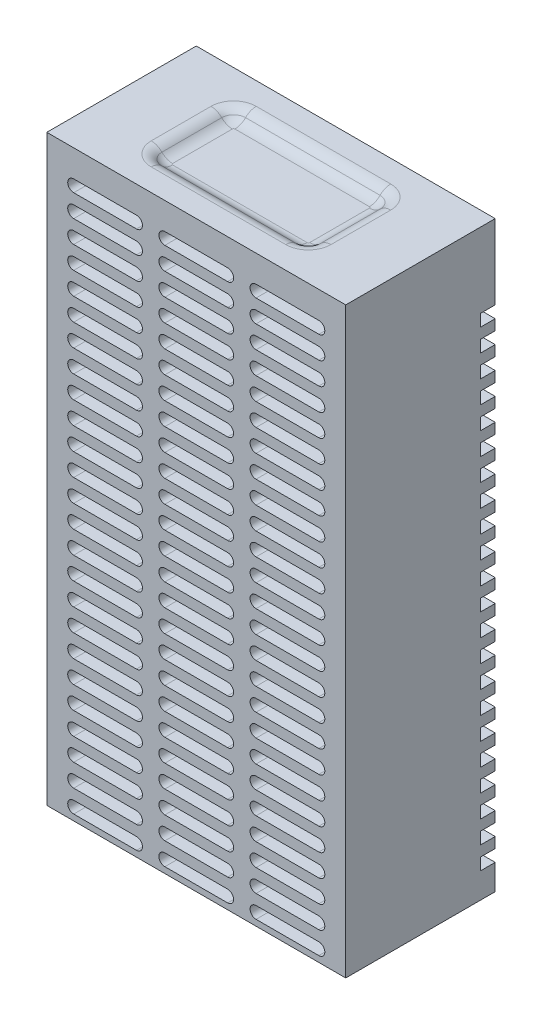
SolidWorks part; units mm, degrees
material "Plain Carbon Steel"
ref_plane "Front Plane" through (0, 0, 0) normal (0, 0, 1) x (1, 0, 0)
ref_plane "Top Plane" through (0, 0, 0) normal (0, 1, 0) x (1, 0, 0)
ref_plane "Right Plane" through (0, 0, 0) normal (1, 0, 0) x (0, 0, -1)
sketch "Sketch1" plane through (0, 0, 0) normal (0, 0, 1) x (1, 0, 0)
  line L1 (50, -97.5) -> (-50, -97.5)
  line L2 (50, -97.5) -> (50, 97.5)
  line L3 (50, 97.5) -> (-50, 97.5)
  line L4 (-50, -97.5) -> (-50, 97.5)
  line L5 (50, -97.5) -> (-50, 97.5) construction
  line L6 (50, 97.5) -> (-50, -97.5) construction
  point P0 (0, 0)
  dimension "D1" = 100
  dimension "D2" = 195
extrude "Boss-Extrude1" add sketch "Sketch1" along normal blind 50
sketch "Sketch2" plane through (0, 0, 50) normal (0, 0, 1) x (1, 0, 0)
  line L0 (-50, 88.5) -> (50, 88.5) construction
  line L1 (-50, 97.5) -> (-50, -97.5) construction
  line L2 (50, -97.5) -> (50, 97.5) construction
  line L3 (50, 97.5) -> (-50, 97.5) construction
  line L4 (0, 97.5) -> (0, -97.5) construction
  line L5 (-50, -97.5) -> (50, -97.5) construction
  line L6 (10.5, 86.5) -> (-10.5, 86.5) construction
  line L7 (10.5, 84.5) -> (-10.5, 84.5)
  line L8 (10.5, 88.5) -> (-10.5, 88.5)
  line L9 (-41, 86.5) -> (-20, 86.5) construction
  line L10 (-41, 88.5) -> (-20, 88.5)
  line L11 (-41, 84.5) -> (-20, 84.5)
  line L12 (41, 86.5) -> (20, 86.5) construction
  line L13 (41, 88.5) -> (20, 88.5)
  line L14 (41, 84.5) -> (20, 84.5)
  line L15 (10.5, 79) -> (-10.5, 79) construction
  line L16 (10.5, 77) -> (-10.5, 77)
  line L17 (10.5, 81) -> (-10.5, 81)
  line L18 (-41, 79) -> (-20, 79) construction
  line L19 (-41, 81) -> (-20, 81)
  line L20 (-41, 77) -> (-20, 77)
  line L21 (41, 79) -> (20, 79) construction
  line L22 (41, 81) -> (20, 81)
  line L23 (41, 77) -> (20, 77)
  line L24 (10.5, 71.5) -> (-10.5, 71.5) construction
  line L25 (10.5, 69.5) -> (-10.5, 69.5)
  line L26 (10.5, 73.5) -> (-10.5, 73.5)
  line L27 (-41, 71.5) -> (-20, 71.5) construction
  line L28 (-41, 73.5) -> (-20, 73.5)
  line L29 (-41, 69.5) -> (-20, 69.5)
  line L30 (41, 71.5) -> (20, 71.5) construction
  line L31 (41, 73.5) -> (20, 73.5)
  line L32 (41, 69.5) -> (20, 69.5)
  line L33 (10.5, 64) -> (-10.5, 64) construction
  line L34 (10.5, 62) -> (-10.5, 62)
  line L35 (10.5, 66) -> (-10.5, 66)
  line L36 (-41, 64) -> (-20, 64) construction
  line L37 (-41, 66) -> (-20, 66)
  line L38 (-41, 62) -> (-20, 62)
  line L39 (41, 64) -> (20, 64) construction
  line L40 (41, 66) -> (20, 66)
  line L41 (41, 62) -> (20, 62)
  line L42 (10.5, 56.5) -> (-10.5, 56.5) construction
  line L43 (10.5, 54.5) -> (-10.5, 54.5)
  line L44 (10.5, 58.5) -> (-10.5, 58.5)
  line L45 (-41, 56.5) -> (-20, 56.5) construction
  line L46 (-41, 58.5) -> (-20, 58.5)
  line L47 (-41, 54.5) -> (-20, 54.5)
  line L48 (41, 56.5) -> (20, 56.5) construction
  line L49 (41, 58.5) -> (20, 58.5)
  line L50 (41, 54.5) -> (20, 54.5)
  line L51 (10.5, 49) -> (-10.5, 49) construction
  line L52 (10.5, 47) -> (-10.5, 47)
  line L53 (10.5, 51) -> (-10.5, 51)
  line L54 (-41, 49) -> (-20, 49) construction
  line L55 (-41, 51) -> (-20, 51)
  line L56 (-41, 47) -> (-20, 47)
  line L57 (41, 49) -> (20, 49) construction
  line L58 (41, 51) -> (20, 51)
  line L59 (41, 47) -> (20, 47)
  line L60 (10.5, 41.5) -> (-10.5, 41.5) construction
  line L61 (10.5, 39.5) -> (-10.5, 39.5)
  line L62 (10.5, 43.5) -> (-10.5, 43.5)
  line L63 (-41, 41.5) -> (-20, 41.5) construction
  line L64 (-41, 43.5) -> (-20, 43.5)
  line L65 (-41, 39.5) -> (-20, 39.5)
  line L66 (41, 41.5) -> (20, 41.5) construction
  line L67 (41, 43.5) -> (20, 43.5)
  line L68 (41, 39.5) -> (20, 39.5)
  line L69 (10.5, 34) -> (-10.5, 34) construction
  line L70 (10.5, 32) -> (-10.5, 32)
  line L71 (10.5, 36) -> (-10.5, 36)
  line L72 (-41, 34) -> (-20, 34) construction
  line L73 (-41, 36) -> (-20, 36)
  line L74 (-41, 32) -> (-20, 32)
  line L75 (41, 34) -> (20, 34) construction
  line L76 (41, 36) -> (20, 36)
  line L77 (41, 32) -> (20, 32)
  line L78 (10.5, 26.5) -> (-10.5, 26.5) construction
  line L79 (10.5, 24.5) -> (-10.5, 24.5)
  line L80 (10.5, 28.5) -> (-10.5, 28.5)
  line L81 (-41, 26.5) -> (-20, 26.5) construction
  line L82 (-41, 28.5) -> (-20, 28.5)
  line L83 (-41, 24.5) -> (-20, 24.5)
  line L84 (41, 26.5) -> (20, 26.5) construction
  line L85 (41, 28.5) -> (20, 28.5)
  line L86 (41, 24.5) -> (20, 24.5)
  line L87 (10.5, 19) -> (-10.5, 19) construction
  line L88 (10.5, 17) -> (-10.5, 17)
  line L89 (10.5, 21) -> (-10.5, 21)
  line L90 (-41, 19) -> (-20, 19) construction
  line L91 (-41, 21) -> (-20, 21)
  line L92 (-41, 17) -> (-20, 17)
  line L93 (41, 19) -> (20, 19) construction
  line L94 (41, 21) -> (20, 21)
  line L95 (41, 17) -> (20, 17)
  line L96 (10.5, 11.5) -> (-10.5, 11.5) construction
  line L97 (10.5, 9.5) -> (-10.5, 9.5)
  line L98 (10.5, 13.5) -> (-10.5, 13.5)
  line L99 (-41, 11.5) -> (-20, 11.5) construction
  line L100 (-41, 13.5) -> (-20, 13.5)
  line L101 (-41, 9.5) -> (-20, 9.5)
  line L102 (41, 11.5) -> (20, 11.5) construction
  line L103 (41, 13.5) -> (20, 13.5)
  line L104 (41, 9.5) -> (20, 9.5)
  line L105 (10.5, 4) -> (-10.5, 4) construction
  line L106 (10.5, 2) -> (-10.5, 2)
  line L107 (10.5, 6) -> (-10.5, 6)
  line L108 (-41, 4) -> (-20, 4) construction
  line L109 (-41, 6) -> (-20, 6)
  line L110 (-41, 2) -> (-20, 2)
  line L111 (41, 4) -> (20, 4) construction
  line L112 (41, 6) -> (20, 6)
  line L113 (41, 2) -> (20, 2)
  line L114 (10.5, -3.5) -> (-10.5, -3.5) construction
  line L115 (10.5, -5.5) -> (-10.5, -5.5)
  line L116 (10.5, -1.5) -> (-10.5, -1.5)
  line L117 (-41, -3.5) -> (-20, -3.5) construction
  line L118 (-41, -1.5) -> (-20, -1.5)
  line L119 (-41, -5.5) -> (-20, -5.5)
  line L120 (41, -3.5) -> (20, -3.5) construction
  line L121 (41, -1.5) -> (20, -1.5)
  line L122 (41, -5.5) -> (20, -5.5)
  line L123 (10.5, -11) -> (-10.5, -11) construction
  line L124 (10.5, -13) -> (-10.5, -13)
  line L125 (10.5, -9) -> (-10.5, -9)
  line L126 (-41, -11) -> (-20, -11) construction
  line L127 (-41, -9) -> (-20, -9)
  line L128 (-41, -13) -> (-20, -13)
  line L129 (41, -11) -> (20, -11) construction
  line L130 (41, -9) -> (20, -9)
  line L131 (41, -13) -> (20, -13)
  line L132 (10.5, -18.5) -> (-10.5, -18.5) construction
  line L133 (10.5, -20.5) -> (-10.5, -20.5)
  line L134 (10.5, -16.5) -> (-10.5, -16.5)
  line L135 (-41, -18.5) -> (-20, -18.5) construction
  line L136 (-41, -16.5) -> (-20, -16.5)
  line L137 (-41, -20.5) -> (-20, -20.5)
  line L138 (41, -18.5) -> (20, -18.5) construction
  line L139 (41, -16.5) -> (20, -16.5)
  line L140 (41, -20.5) -> (20, -20.5)
  line L141 (10.5, -26) -> (-10.5, -26) construction
  line L142 (10.5, -28) -> (-10.5, -28)
  line L143 (10.5, -24) -> (-10.5, -24)
  line L144 (-41, -26) -> (-20, -26) construction
  line L145 (-41, -24) -> (-20, -24)
  line L146 (-41, -28) -> (-20, -28)
  line L147 (41, -26) -> (20, -26) construction
  line L148 (41, -24) -> (20, -24)
  line L149 (41, -28) -> (20, -28)
  line L150 (10.5, -33.5) -> (-10.5, -33.5) construction
  line L151 (10.5, -35.5) -> (-10.5, -35.5)
  line L152 (10.5, -31.5) -> (-10.5, -31.5)
  line L153 (-41, -33.5) -> (-20, -33.5) construction
  line L154 (-41, -31.5) -> (-20, -31.5)
  line L155 (-41, -35.5) -> (-20, -35.5)
  line L156 (41, -33.5) -> (20, -33.5) construction
  line L157 (41, -31.5) -> (20, -31.5)
  line L158 (41, -35.5) -> (20, -35.5)
  line L159 (10.5, -41) -> (-10.5, -41) construction
  line L160 (10.5, -43) -> (-10.5, -43)
  line L161 (10.5, -39) -> (-10.5, -39)
  line L162 (-41, -41) -> (-20, -41) construction
  line L163 (-41, -39) -> (-20, -39)
  line L164 (-41, -43) -> (-20, -43)
  line L165 (41, -41) -> (20, -41) construction
  line L166 (41, -39) -> (20, -39)
  line L167 (41, -43) -> (20, -43)
  line L168 (10.5, -48.5) -> (-10.5, -48.5) construction
  line L169 (10.5, -50.5) -> (-10.5, -50.5)
  line L170 (10.5, -46.5) -> (-10.5, -46.5)
  line L171 (-41, -48.5) -> (-20, -48.5) construction
  line L172 (-41, -46.5) -> (-20, -46.5)
  line L173 (-41, -50.5) -> (-20, -50.5)
  line L174 (41, -48.5) -> (20, -48.5) construction
  line L175 (41, -46.5) -> (20, -46.5)
  line L176 (41, -50.5) -> (20, -50.5)
  line L177 (10.5, -56) -> (-10.5, -56) construction
  line L178 (10.5, -58) -> (-10.5, -58)
  line L179 (10.5, -54) -> (-10.5, -54)
  line L180 (-41, -56) -> (-20, -56) construction
  line L181 (-41, -54) -> (-20, -54)
  line L182 (-41, -58) -> (-20, -58)
  line L183 (41, -56) -> (20, -56) construction
  line L184 (41, -54) -> (20, -54)
  line L185 (41, -58) -> (20, -58)
  line L186 (10.5, -63.5) -> (-10.5, -63.5) construction
  line L187 (10.5, -65.5) -> (-10.5, -65.5)
  line L188 (10.5, -61.5) -> (-10.5, -61.5)
  line L189 (-41, -63.5) -> (-20, -63.5) construction
  line L190 (-41, -61.5) -> (-20, -61.5)
  line L191 (-41, -65.5) -> (-20, -65.5)
  line L192 (41, -63.5) -> (20, -63.5) construction
  line L193 (41, -61.5) -> (20, -61.5)
  line L194 (41, -65.5) -> (20, -65.5)
  line L195 (10.5, -71) -> (-10.5, -71) construction
  line L196 (10.5, -73) -> (-10.5, -73)
  line L197 (10.5, -69) -> (-10.5, -69)
  line L198 (-41, -71) -> (-20, -71) construction
  line L199 (-41, -69) -> (-20, -69)
  line L200 (-41, -73) -> (-20, -73)
  line L201 (41, -71) -> (20, -71) construction
  line L202 (41, -69) -> (20, -69)
  line L203 (41, -73) -> (20, -73)
  line L204 (10.5, -78.5) -> (-10.5, -78.5) construction
  line L205 (10.5, -80.5) -> (-10.5, -80.5)
  line L206 (10.5, -76.5) -> (-10.5, -76.5)
  line L207 (-41, -78.5) -> (-20, -78.5) construction
  line L208 (-41, -76.5) -> (-20, -76.5)
  line L209 (-41, -80.5) -> (-20, -80.5)
  line L210 (41, -78.5) -> (20, -78.5) construction
  line L211 (41, -76.5) -> (20, -76.5)
  line L212 (41, -80.5) -> (20, -80.5)
  line L213 (10.5, -86) -> (-10.5, -86) construction
  line L214 (10.5, -88) -> (-10.5, -88)
  line L215 (10.5, -84) -> (-10.5, -84)
  line L216 (-41, -86) -> (-20, -86) construction
  line L217 (-41, -84) -> (-20, -84)
  line L218 (-41, -88) -> (-20, -88)
  line L219 (41, -86) -> (20, -86) construction
  line L220 (41, -84) -> (20, -84)
  line L221 (41, -88) -> (20, -88)
  line L222 (10.5, -93.5) -> (-10.5, -93.5) construction
  line L223 (10.5, -95.5) -> (-10.5, -95.5)
  line L224 (10.5, -91.5) -> (-10.5, -91.5)
  line L225 (-41, -93.5) -> (-20, -93.5) construction
  line L226 (-41, -91.5) -> (-20, -91.5)
  line L227 (-41, -95.5) -> (-20, -95.5)
  line L228 (41, -93.5) -> (20, -93.5) construction
  line L229 (41, -91.5) -> (20, -91.5)
  line L230 (41, -95.5) -> (20, -95.5)
  arc A0 (10.5, 84.5) -> (10.5, 88.5) centre (10.5, 86.5) ccw
  arc A1 (-10.5, 88.5) -> (-10.5, 84.5) centre (-10.5, 86.5) ccw
  arc A2 (-41, 88.5) -> (-41, 84.5) centre (-41, 86.5) ccw
  arc A3 (-20, 84.5) -> (-20, 88.5) centre (-20, 86.5) ccw
  arc A4 (41, 88.5) -> (41, 84.5) centre (41, 86.5) cw
  arc A5 (20, 84.5) -> (20, 88.5) centre (20, 86.5) cw
  arc A6 (10.5, 77) -> (10.5, 81) centre (10.5, 79) ccw
  arc A7 (-10.5, 81) -> (-10.5, 77) centre (-10.5, 79) ccw
  arc A8 (-41, 81) -> (-41, 77) centre (-41, 79) ccw
  arc A9 (-20, 77) -> (-20, 81) centre (-20, 79) ccw
  arc A10 (41, 81) -> (41, 77) centre (41, 79) cw
  arc A11 (20, 77) -> (20, 81) centre (20, 79) cw
  arc A12 (10.5, 69.5) -> (10.5, 73.5) centre (10.5, 71.5) ccw
  arc A13 (-10.5, 73.5) -> (-10.5, 69.5) centre (-10.5, 71.5) ccw
  arc A14 (-41, 73.5) -> (-41, 69.5) centre (-41, 71.5) ccw
  arc A15 (-20, 69.5) -> (-20, 73.5) centre (-20, 71.5) ccw
  arc A16 (41, 73.5) -> (41, 69.5) centre (41, 71.5) cw
  arc A17 (20, 69.5) -> (20, 73.5) centre (20, 71.5) cw
  arc A18 (10.5, 62) -> (10.5, 66) centre (10.5, 64) ccw
  arc A19 (-10.5, 66) -> (-10.5, 62) centre (-10.5, 64) ccw
  arc A20 (-41, 66) -> (-41, 62) centre (-41, 64) ccw
  arc A21 (-20, 62) -> (-20, 66) centre (-20, 64) ccw
  arc A22 (41, 66) -> (41, 62) centre (41, 64) cw
  arc A23 (20, 62) -> (20, 66) centre (20, 64) cw
  arc A24 (10.5, 54.5) -> (10.5, 58.5) centre (10.5, 56.5) ccw
  arc A25 (-10.5, 58.5) -> (-10.5, 54.5) centre (-10.5, 56.5) ccw
  arc A26 (-41, 58.5) -> (-41, 54.5) centre (-41, 56.5) ccw
  arc A27 (-20, 54.5) -> (-20, 58.5) centre (-20, 56.5) ccw
  arc A28 (41, 58.5) -> (41, 54.5) centre (41, 56.5) cw
  arc A29 (20, 54.5) -> (20, 58.5) centre (20, 56.5) cw
  arc A30 (10.5, 47) -> (10.5, 51) centre (10.5, 49) ccw
  arc A31 (-10.5, 51) -> (-10.5, 47) centre (-10.5, 49) ccw
  arc A32 (-41, 51) -> (-41, 47) centre (-41, 49) ccw
  arc A33 (-20, 47) -> (-20, 51) centre (-20, 49) ccw
  arc A34 (41, 51) -> (41, 47) centre (41, 49) cw
  arc A35 (20, 47) -> (20, 51) centre (20, 49) cw
  arc A36 (10.5, 39.5) -> (10.5, 43.5) centre (10.5, 41.5) ccw
  arc A37 (-10.5, 43.5) -> (-10.5, 39.5) centre (-10.5, 41.5) ccw
  arc A38 (-41, 43.5) -> (-41, 39.5) centre (-41, 41.5) ccw
  arc A39 (-20, 39.5) -> (-20, 43.5) centre (-20, 41.5) ccw
  arc A40 (41, 43.5) -> (41, 39.5) centre (41, 41.5) cw
  arc A41 (20, 39.5) -> (20, 43.5) centre (20, 41.5) cw
  arc A42 (10.5, 32) -> (10.5, 36) centre (10.5, 34) ccw
  arc A43 (-10.5, 36) -> (-10.5, 32) centre (-10.5, 34) ccw
  arc A44 (-41, 36) -> (-41, 32) centre (-41, 34) ccw
  arc A45 (-20, 32) -> (-20, 36) centre (-20, 34) ccw
  arc A46 (41, 36) -> (41, 32) centre (41, 34) cw
  arc A47 (20, 32) -> (20, 36) centre (20, 34) cw
  arc A48 (10.5, 24.5) -> (10.5, 28.5) centre (10.5, 26.5) ccw
  arc A49 (-10.5, 28.5) -> (-10.5, 24.5) centre (-10.5, 26.5) ccw
  arc A50 (-41, 28.5) -> (-41, 24.5) centre (-41, 26.5) ccw
  arc A51 (-20, 24.5) -> (-20, 28.5) centre (-20, 26.5) ccw
  arc A52 (41, 28.5) -> (41, 24.5) centre (41, 26.5) cw
  arc A53 (20, 24.5) -> (20, 28.5) centre (20, 26.5) cw
  arc A54 (10.5, 17) -> (10.5, 21) centre (10.5, 19) ccw
  arc A55 (-10.5, 21) -> (-10.5, 17) centre (-10.5, 19) ccw
  arc A56 (-41, 21) -> (-41, 17) centre (-41, 19) ccw
  arc A57 (-20, 17) -> (-20, 21) centre (-20, 19) ccw
  arc A58 (41, 21) -> (41, 17) centre (41, 19) cw
  arc A59 (20, 17) -> (20, 21) centre (20, 19) cw
  arc A60 (10.5, 9.5) -> (10.5, 13.5) centre (10.5, 11.5) ccw
  arc A61 (-10.5, 13.5) -> (-10.5, 9.5) centre (-10.5, 11.5) ccw
  arc A62 (-41, 13.5) -> (-41, 9.5) centre (-41, 11.5) ccw
  arc A63 (-20, 9.5) -> (-20, 13.5) centre (-20, 11.5) ccw
  arc A64 (41, 13.5) -> (41, 9.5) centre (41, 11.5) cw
  arc A65 (20, 9.5) -> (20, 13.5) centre (20, 11.5) cw
  arc A66 (10.5, 2) -> (10.5, 6) centre (10.5, 4) ccw
  arc A67 (-10.5, 6) -> (-10.5, 2) centre (-10.5, 4) ccw
  arc A68 (-41, 6) -> (-41, 2) centre (-41, 4) ccw
  arc A69 (-20, 2) -> (-20, 6) centre (-20, 4) ccw
  arc A70 (41, 6) -> (41, 2) centre (41, 4) cw
  arc A71 (20, 2) -> (20, 6) centre (20, 4) cw
  arc A72 (10.5, -5.5) -> (10.5, -1.5) centre (10.5, -3.5) ccw
  arc A73 (-10.5, -1.5) -> (-10.5, -5.5) centre (-10.5, -3.5) ccw
  arc A74 (-41, -1.5) -> (-41, -5.5) centre (-41, -3.5) ccw
  arc A75 (-20, -5.5) -> (-20, -1.5) centre (-20, -3.5) ccw
  arc A76 (41, -1.5) -> (41, -5.5) centre (41, -3.5) cw
  arc A77 (20, -5.5) -> (20, -1.5) centre (20, -3.5) cw
  arc A78 (10.5, -13) -> (10.5, -9) centre (10.5, -11) ccw
  arc A79 (-10.5, -9) -> (-10.5, -13) centre (-10.5, -11) ccw
  arc A80 (-41, -9) -> (-41, -13) centre (-41, -11) ccw
  arc A81 (-20, -13) -> (-20, -9) centre (-20, -11) ccw
  arc A82 (41, -9) -> (41, -13) centre (41, -11) cw
  arc A83 (20, -13) -> (20, -9) centre (20, -11) cw
  arc A84 (10.5, -20.5) -> (10.5, -16.5) centre (10.5, -18.5) ccw
  arc A85 (-10.5, -16.5) -> (-10.5, -20.5) centre (-10.5, -18.5) ccw
  arc A86 (-41, -16.5) -> (-41, -20.5) centre (-41, -18.5) ccw
  arc A87 (-20, -20.5) -> (-20, -16.5) centre (-20, -18.5) ccw
  arc A88 (41, -16.5) -> (41, -20.5) centre (41, -18.5) cw
  arc A89 (20, -20.5) -> (20, -16.5) centre (20, -18.5) cw
  arc A90 (10.5, -28) -> (10.5, -24) centre (10.5, -26) ccw
  arc A91 (-10.5, -24) -> (-10.5, -28) centre (-10.5, -26) ccw
  arc A92 (-41, -24) -> (-41, -28) centre (-41, -26) ccw
  arc A93 (-20, -28) -> (-20, -24) centre (-20, -26) ccw
  arc A94 (41, -24) -> (41, -28) centre (41, -26) cw
  arc A95 (20, -28) -> (20, -24) centre (20, -26) cw
  arc A96 (10.5, -35.5) -> (10.5, -31.5) centre (10.5, -33.5) ccw
  arc A97 (-10.5, -31.5) -> (-10.5, -35.5) centre (-10.5, -33.5) ccw
  arc A98 (-41, -31.5) -> (-41, -35.5) centre (-41, -33.5) ccw
  arc A99 (-20, -35.5) -> (-20, -31.5) centre (-20, -33.5) ccw
  arc A100 (41, -31.5) -> (41, -35.5) centre (41, -33.5) cw
  arc A101 (20, -35.5) -> (20, -31.5) centre (20, -33.5) cw
  arc A102 (10.5, -43) -> (10.5, -39) centre (10.5, -41) ccw
  arc A103 (-10.5, -39) -> (-10.5, -43) centre (-10.5, -41) ccw
  arc A104 (-41, -39) -> (-41, -43) centre (-41, -41) ccw
  arc A105 (-20, -43) -> (-20, -39) centre (-20, -41) ccw
  arc A106 (41, -39) -> (41, -43) centre (41, -41) cw
  arc A107 (20, -43) -> (20, -39) centre (20, -41) cw
  arc A108 (10.5, -50.5) -> (10.5, -46.5) centre (10.5, -48.5) ccw
  arc A109 (-10.5, -46.5) -> (-10.5, -50.5) centre (-10.5, -48.5) ccw
  arc A110 (-41, -46.5) -> (-41, -50.5) centre (-41, -48.5) ccw
  arc A111 (-20, -50.5) -> (-20, -46.5) centre (-20, -48.5) ccw
  arc A112 (41, -46.5) -> (41, -50.5) centre (41, -48.5) cw
  arc A113 (20, -50.5) -> (20, -46.5) centre (20, -48.5) cw
  arc A114 (10.5, -58) -> (10.5, -54) centre (10.5, -56) ccw
  arc A115 (-10.5, -54) -> (-10.5, -58) centre (-10.5, -56) ccw
  arc A116 (-41, -54) -> (-41, -58) centre (-41, -56) ccw
  arc A117 (-20, -58) -> (-20, -54) centre (-20, -56) ccw
  arc A118 (41, -54) -> (41, -58) centre (41, -56) cw
  arc A119 (20, -58) -> (20, -54) centre (20, -56) cw
  arc A120 (10.5, -65.5) -> (10.5, -61.5) centre (10.5, -63.5) ccw
  arc A121 (-10.5, -61.5) -> (-10.5, -65.5) centre (-10.5, -63.5) ccw
  arc A122 (-41, -61.5) -> (-41, -65.5) centre (-41, -63.5) ccw
  arc A123 (-20, -65.5) -> (-20, -61.5) centre (-20, -63.5) ccw
  arc A124 (41, -61.5) -> (41, -65.5) centre (41, -63.5) cw
  arc A125 (20, -65.5) -> (20, -61.5) centre (20, -63.5) cw
  arc A126 (10.5, -73) -> (10.5, -69) centre (10.5, -71) ccw
  arc A127 (-10.5, -69) -> (-10.5, -73) centre (-10.5, -71) ccw
  arc A128 (-41, -69) -> (-41, -73) centre (-41, -71) ccw
  arc A129 (-20, -73) -> (-20, -69) centre (-20, -71) ccw
  arc A130 (41, -69) -> (41, -73) centre (41, -71) cw
  arc A131 (20, -73) -> (20, -69) centre (20, -71) cw
  arc A132 (10.5, -80.5) -> (10.5, -76.5) centre (10.5, -78.5) ccw
  arc A133 (-10.5, -76.5) -> (-10.5, -80.5) centre (-10.5, -78.5) ccw
  arc A134 (-41, -76.5) -> (-41, -80.5) centre (-41, -78.5) ccw
  arc A135 (-20, -80.5) -> (-20, -76.5) centre (-20, -78.5) ccw
  arc A136 (41, -76.5) -> (41, -80.5) centre (41, -78.5) cw
  arc A137 (20, -80.5) -> (20, -76.5) centre (20, -78.5) cw
  arc A138 (10.5, -88) -> (10.5, -84) centre (10.5, -86) ccw
  arc A139 (-10.5, -84) -> (-10.5, -88) centre (-10.5, -86) ccw
  arc A140 (-41, -84) -> (-41, -88) centre (-41, -86) ccw
  arc A141 (-20, -88) -> (-20, -84) centre (-20, -86) ccw
  arc A142 (41, -84) -> (41, -88) centre (41, -86) cw
  arc A143 (20, -88) -> (20, -84) centre (20, -86) cw
  arc A144 (10.5, -95.5) -> (10.5, -91.5) centre (10.5, -93.5) ccw
  arc A145 (-10.5, -91.5) -> (-10.5, -95.5) centre (-10.5, -93.5) ccw
  arc A146 (-41, -91.5) -> (-41, -95.5) centre (-41, -93.5) ccw
  arc A147 (-20, -95.5) -> (-20, -91.5) centre (-20, -93.5) ccw
  arc A148 (41, -91.5) -> (41, -95.5) centre (41, -93.5) cw
  arc A149 (20, -95.5) -> (20, -91.5) centre (20, -93.5) cw
  point P14 (0, 86.5)
  point P21 (-30.5, 86.5)
  point P26 (-43, 86.5)
  point P27 (-18, 86.5)
  point P28 (12.5, 86.5)
  point P29 (-12.5, 86.5)
  point P32 (30.5, 86.5)
  point P40 (0, 79)
  point P47 (-30.5, 79)
  point P54 (30.5, 79)
  point P61 (0, 71.5)
  point P68 (-30.5, 71.5)
  point P75 (30.5, 71.5)
  point P82 (0, 64)
  point P89 (-30.5, 64)
  point P96 (30.5, 64)
  point P103 (0, 56.5)
  point P110 (-30.5, 56.5)
  point P117 (30.5, 56.5)
  point P124 (0, 49)
  point P131 (-30.5, 49)
  point P138 (30.5, 49)
  point P145 (0, 41.5)
  point P152 (-30.5, 41.5)
  point P159 (30.5, 41.5)
  point P166 (0, 34)
  point P173 (-30.5, 34)
  point P180 (30.5, 34)
  point P187 (0, 26.5)
  point P194 (-30.5, 26.5)
  point P201 (30.5, 26.5)
  point P208 (0, 19)
  point P215 (-30.5, 19)
  point P222 (30.5, 19)
  point P229 (0, 11.5)
  point P236 (-30.5, 11.5)
  point P243 (30.5, 11.5)
  point P250 (0, 4)
  point P257 (-30.5, 4)
  point P264 (30.5, 4)
  point P271 (0, -3.5)
  point P278 (-30.5, -3.5)
  point P285 (30.5, -3.5)
  point P292 (0, -11)
  point P299 (-30.5, -11)
  point P306 (30.5, -11)
  point P313 (0, -18.5)
  point P320 (-30.5, -18.5)
  point P327 (30.5, -18.5)
  point P334 (0, -26)
  point P341 (-30.5, -26)
  point P348 (30.5, -26)
  point P355 (0, -33.5)
  point P362 (-30.5, -33.5)
  point P369 (30.5, -33.5)
  point P376 (0, -41)
  point P383 (-30.5, -41)
  point P390 (30.5, -41)
  point P397 (0, -48.5)
  point P404 (-30.5, -48.5)
  point P411 (30.5, -48.5)
  point P418 (0, -56)
  point P425 (-30.5, -56)
  point P432 (30.5, -56)
  point P439 (0, -63.5)
  point P446 (-30.5, -63.5)
  point P453 (30.5, -63.5)
  point P460 (0, -71)
  point P467 (-30.5, -71)
  point P474 (30.5, -71)
  point P481 (0, -78.5)
  point P488 (-30.5, -78.5)
  point P495 (30.5, -78.5)
  point P502 (0, -86)
  point P509 (-30.5, -86)
  point P516 (30.5, -86)
  point P523 (0, -93.5)
  point P530 (-30.5, -93.5)
  point P537 (30.5, -93.5)
  dimension "D1" = 9
  dimension "D2" = 4
  dimension "D3" = 4
  dimension "D4" = 25
  dimension "D5" = 25
  dimension "D6" = 7
  dimension "D7" = 25
extrude "Cut-Extrude1" cut sketch "Sketch2" against normal blind 20
sketch "Sketch3" plane through (0, 0, 0) normal (0, 0, -1) x (-1, 0, 0)
  line L0 (0, 97.5) -> (0, -97.5) construction
  line L1 (-50, 97.5) -> (50, 97.5) construction
  line L2 (50, -97.5) -> (-50, -97.5) construction
  line L3 (50, 70.5) -> (27, 70.5) construction
  line L4 (50, 97.5) -> (50, -97.5) construction
  line L5 (50, 68.5) -> (27, 68.5)
  line L6 (50, 72.5) -> (27, 72.5)
  line L7 (-50, 70.5) -> (-27, 70.5) construction
  line L8 (-50, 68.5) -> (-27, 68.5)
  line L9 (-50, 72.5) -> (-27, 72.5)
  line L10 (50, 63) -> (27, 63) construction
  line L11 (50, 61) -> (27, 61)
  line L12 (50, 65) -> (27, 65)
  line L13 (-50, 63) -> (-27, 63) construction
  line L14 (-50, 61) -> (-27, 61)
  line L15 (-50, 65) -> (-27, 65)
  line L16 (50, 55.5) -> (27, 55.5) construction
  line L17 (50, 53.5) -> (27, 53.5)
  line L18 (50, 57.5) -> (27, 57.5)
  line L19 (-50, 55.5) -> (-27, 55.5) construction
  line L20 (-50, 53.5) -> (-27, 53.5)
  line L21 (-50, 57.5) -> (-27, 57.5)
  line L22 (50, 48) -> (27, 48) construction
  line L23 (50, 46) -> (27, 46)
  line L24 (50, 50) -> (27, 50)
  line L25 (-50, 48) -> (-27, 48) construction
  line L26 (-50, 46) -> (-27, 46)
  line L27 (-50, 50) -> (-27, 50)
  line L28 (50, 40.5) -> (27, 40.5) construction
  line L29 (50, 38.5) -> (27, 38.5)
  line L30 (50, 42.5) -> (27, 42.5)
  line L31 (-50, 40.5) -> (-27, 40.5) construction
  line L32 (-50, 38.5) -> (-27, 38.5)
  line L33 (-50, 42.5) -> (-27, 42.5)
  line L34 (50, 33) -> (27, 33) construction
  line L35 (50, 31) -> (27, 31)
  line L36 (50, 35) -> (27, 35)
  line L37 (-50, 33) -> (-27, 33) construction
  line L38 (-50, 31) -> (-27, 31)
  line L39 (-50, 35) -> (-27, 35)
  line L40 (50, 25.5) -> (27, 25.5) construction
  line L41 (50, 23.5) -> (27, 23.5)
  line L42 (50, 27.5) -> (27, 27.5)
  line L43 (-50, 25.5) -> (-27, 25.5) construction
  line L44 (-50, 23.5) -> (-27, 23.5)
  line L45 (-50, 27.5) -> (-27, 27.5)
  line L46 (50, 18) -> (27, 18) construction
  line L47 (50, 16) -> (27, 16)
  line L48 (50, 20) -> (27, 20)
  line L49 (-50, 18) -> (-27, 18) construction
  line L50 (-50, 16) -> (-27, 16)
  line L51 (-50, 20) -> (-27, 20)
  line L52 (50, 10.5) -> (27, 10.5) construction
  line L53 (50, 8.5) -> (27, 8.5)
  line L54 (50, 12.5) -> (27, 12.5)
  line L55 (-50, 10.5) -> (-27, 10.5) construction
  line L56 (-50, 8.5) -> (-27, 8.5)
  line L57 (-50, 12.5) -> (-27, 12.5)
  line L58 (50, 3) -> (27, 3) construction
  line L59 (50, 1) -> (27, 1)
  line L60 (50, 5) -> (27, 5)
  line L61 (-50, 3) -> (-27, 3) construction
  line L62 (-50, 1) -> (-27, 1)
  line L63 (-50, 5) -> (-27, 5)
  line L64 (50, -4.5) -> (27, -4.5) construction
  line L65 (50, -6.5) -> (27, -6.5)
  line L66 (50, -2.5) -> (27, -2.5)
  line L67 (-50, -4.5) -> (-27, -4.5) construction
  line L68 (-50, -6.5) -> (-27, -6.5)
  line L69 (-50, -2.5) -> (-27, -2.5)
  line L70 (50, -12) -> (27, -12) construction
  line L71 (50, -14) -> (27, -14)
  line L72 (50, -10) -> (27, -10)
  line L73 (-50, -12) -> (-27, -12) construction
  line L74 (-50, -14) -> (-27, -14)
  line L75 (-50, -10) -> (-27, -10)
  line L76 (50, -19.5) -> (27, -19.5) construction
  line L77 (50, -21.5) -> (27, -21.5)
  line L78 (50, -17.5) -> (27, -17.5)
  line L79 (-50, -19.5) -> (-27, -19.5) construction
  line L80 (-50, -21.5) -> (-27, -21.5)
  line L81 (-50, -17.5) -> (-27, -17.5)
  line L82 (50, -27) -> (27, -27) construction
  line L83 (50, -29) -> (27, -29)
  line L84 (50, -25) -> (27, -25)
  line L85 (-50, -27) -> (-27, -27) construction
  line L86 (-50, -29) -> (-27, -29)
  line L87 (-50, -25) -> (-27, -25)
  line L88 (50, -34.5) -> (27, -34.5) construction
  line L89 (50, -36.5) -> (27, -36.5)
  line L90 (50, -32.5) -> (27, -32.5)
  line L91 (-50, -34.5) -> (-27, -34.5) construction
  line L92 (-50, -36.5) -> (-27, -36.5)
  line L93 (-50, -32.5) -> (-27, -32.5)
  line L94 (50, -42) -> (27, -42) construction
  line L95 (50, -44) -> (27, -44)
  line L96 (50, -40) -> (27, -40)
  line L97 (-50, -42) -> (-27, -42) construction
  line L98 (-50, -44) -> (-27, -44)
  line L99 (-50, -40) -> (-27, -40)
  line L100 (50, -49.5) -> (27, -49.5) construction
  line L101 (50, -51.5) -> (27, -51.5)
  line L102 (50, -47.5) -> (27, -47.5)
  line L103 (-50, -49.5) -> (-27, -49.5) construction
  line L104 (-50, -51.5) -> (-27, -51.5)
  line L105 (-50, -47.5) -> (-27, -47.5)
  line L106 (50, -57) -> (27, -57) construction
  line L107 (50, -59) -> (27, -59)
  line L108 (50, -55) -> (27, -55)
  line L109 (-50, -57) -> (-27, -57) construction
  line L110 (-50, -59) -> (-27, -59)
  line L111 (-50, -55) -> (-27, -55)
  line L112 (50, -64.5) -> (27, -64.5) construction
  line L113 (50, -66.5) -> (27, -66.5)
  line L114 (50, -62.5) -> (27, -62.5)
  line L115 (-50, -64.5) -> (-27, -64.5) construction
  line L116 (-50, -66.5) -> (-27, -66.5)
  line L117 (-50, -62.5) -> (-27, -62.5)
  line L118 (50, -72) -> (27, -72) construction
  line L119 (50, -74) -> (27, -74)
  line L120 (50, -70) -> (27, -70)
  line L121 (-50, -72) -> (-27, -72) construction
  line L122 (-50, -74) -> (-27, -74)
  line L123 (-50, -70) -> (-27, -70)
  line L124 (50, -79.5) -> (27, -79.5) construction
  line L125 (50, -81.5) -> (27, -81.5)
  line L126 (50, -77.5) -> (27, -77.5)
  line L127 (-50, -79.5) -> (-27, -79.5) construction
  line L128 (-50, -81.5) -> (-27, -81.5)
  line L129 (-50, -77.5) -> (-27, -77.5)
  line L130 (50, -87) -> (27, -87) construction
  line L131 (50, -89) -> (27, -89)
  line L132 (50, -85) -> (27, -85)
  line L133 (-50, -87) -> (-27, -87) construction
  line L134 (-50, -89) -> (-27, -89)
  line L135 (-50, -85) -> (-27, -85)
  arc A0 (50, 68.5) -> (50, 72.5) centre (50, 70.5) ccw
  arc A1 (27, 72.5) -> (27, 68.5) centre (27, 70.5) ccw
  arc A2 (-50, 68.5) -> (-50, 72.5) centre (-50, 70.5) cw
  arc A3 (-27, 72.5) -> (-27, 68.5) centre (-27, 70.5) cw
  arc A4 (50, 61) -> (50, 65) centre (50, 63) ccw
  arc A5 (27, 65) -> (27, 61) centre (27, 63) ccw
  arc A6 (-50, 61) -> (-50, 65) centre (-50, 63) cw
  arc A7 (-27, 65) -> (-27, 61) centre (-27, 63) cw
  arc A8 (50, 53.5) -> (50, 57.5) centre (50, 55.5) ccw
  arc A9 (27, 57.5) -> (27, 53.5) centre (27, 55.5) ccw
  arc A10 (-50, 53.5) -> (-50, 57.5) centre (-50, 55.5) cw
  arc A11 (-27, 57.5) -> (-27, 53.5) centre (-27, 55.5) cw
  arc A12 (50, 46) -> (50, 50) centre (50, 48) ccw
  arc A13 (27, 50) -> (27, 46) centre (27, 48) ccw
  arc A14 (-50, 46) -> (-50, 50) centre (-50, 48) cw
  arc A15 (-27, 50) -> (-27, 46) centre (-27, 48) cw
  arc A16 (50, 38.5) -> (50, 42.5) centre (50, 40.5) ccw
  arc A17 (27, 42.5) -> (27, 38.5) centre (27, 40.5) ccw
  arc A18 (-50, 38.5) -> (-50, 42.5) centre (-50, 40.5) cw
  arc A19 (-27, 42.5) -> (-27, 38.5) centre (-27, 40.5) cw
  arc A20 (50, 31) -> (50, 35) centre (50, 33) ccw
  arc A21 (27, 35) -> (27, 31) centre (27, 33) ccw
  arc A22 (-50, 31) -> (-50, 35) centre (-50, 33) cw
  arc A23 (-27, 35) -> (-27, 31) centre (-27, 33) cw
  arc A24 (50, 23.5) -> (50, 27.5) centre (50, 25.5) ccw
  arc A25 (27, 27.5) -> (27, 23.5) centre (27, 25.5) ccw
  arc A26 (-50, 23.5) -> (-50, 27.5) centre (-50, 25.5) cw
  arc A27 (-27, 27.5) -> (-27, 23.5) centre (-27, 25.5) cw
  arc A28 (50, 16) -> (50, 20) centre (50, 18) ccw
  arc A29 (27, 20) -> (27, 16) centre (27, 18) ccw
  arc A30 (-50, 16) -> (-50, 20) centre (-50, 18) cw
  arc A31 (-27, 20) -> (-27, 16) centre (-27, 18) cw
  arc A32 (50, 8.5) -> (50, 12.5) centre (50, 10.5) ccw
  arc A33 (27, 12.5) -> (27, 8.5) centre (27, 10.5) ccw
  arc A34 (-50, 8.5) -> (-50, 12.5) centre (-50, 10.5) cw
  arc A35 (-27, 12.5) -> (-27, 8.5) centre (-27, 10.5) cw
  arc A36 (50, 1) -> (50, 5) centre (50, 3) ccw
  arc A37 (27, 5) -> (27, 1) centre (27, 3) ccw
  arc A38 (-50, 1) -> (-50, 5) centre (-50, 3) cw
  arc A39 (-27, 5) -> (-27, 1) centre (-27, 3) cw
  arc A40 (50, -6.5) -> (50, -2.5) centre (50, -4.5) ccw
  arc A41 (27, -2.5) -> (27, -6.5) centre (27, -4.5) ccw
  arc A42 (-50, -6.5) -> (-50, -2.5) centre (-50, -4.5) cw
  arc A43 (-27, -2.5) -> (-27, -6.5) centre (-27, -4.5) cw
  arc A44 (50, -14) -> (50, -10) centre (50, -12) ccw
  arc A45 (27, -10) -> (27, -14) centre (27, -12) ccw
  arc A46 (-50, -14) -> (-50, -10) centre (-50, -12) cw
  arc A47 (-27, -10) -> (-27, -14) centre (-27, -12) cw
  arc A48 (50, -21.5) -> (50, -17.5) centre (50, -19.5) ccw
  arc A49 (27, -17.5) -> (27, -21.5) centre (27, -19.5) ccw
  arc A50 (-50, -21.5) -> (-50, -17.5) centre (-50, -19.5) cw
  arc A51 (-27, -17.5) -> (-27, -21.5) centre (-27, -19.5) cw
  arc A52 (50, -29) -> (50, -25) centre (50, -27) ccw
  arc A53 (27, -25) -> (27, -29) centre (27, -27) ccw
  arc A54 (-50, -29) -> (-50, -25) centre (-50, -27) cw
  arc A55 (-27, -25) -> (-27, -29) centre (-27, -27) cw
  arc A56 (50, -36.5) -> (50, -32.5) centre (50, -34.5) ccw
  arc A57 (27, -32.5) -> (27, -36.5) centre (27, -34.5) ccw
  arc A58 (-50, -36.5) -> (-50, -32.5) centre (-50, -34.5) cw
  arc A59 (-27, -32.5) -> (-27, -36.5) centre (-27, -34.5) cw
  arc A60 (50, -44) -> (50, -40) centre (50, -42) ccw
  arc A61 (27, -40) -> (27, -44) centre (27, -42) ccw
  arc A62 (-50, -44) -> (-50, -40) centre (-50, -42) cw
  arc A63 (-27, -40) -> (-27, -44) centre (-27, -42) cw
  arc A64 (50, -51.5) -> (50, -47.5) centre (50, -49.5) ccw
  arc A65 (27, -47.5) -> (27, -51.5) centre (27, -49.5) ccw
  arc A66 (-50, -51.5) -> (-50, -47.5) centre (-50, -49.5) cw
  arc A67 (-27, -47.5) -> (-27, -51.5) centre (-27, -49.5) cw
  arc A68 (50, -59) -> (50, -55) centre (50, -57) ccw
  arc A69 (27, -55) -> (27, -59) centre (27, -57) ccw
  arc A70 (-50, -59) -> (-50, -55) centre (-50, -57) cw
  arc A71 (-27, -55) -> (-27, -59) centre (-27, -57) cw
  arc A72 (50, -66.5) -> (50, -62.5) centre (50, -64.5) ccw
  arc A73 (27, -62.5) -> (27, -66.5) centre (27, -64.5) ccw
  arc A74 (-50, -66.5) -> (-50, -62.5) centre (-50, -64.5) cw
  arc A75 (-27, -62.5) -> (-27, -66.5) centre (-27, -64.5) cw
  arc A76 (50, -74) -> (50, -70) centre (50, -72) ccw
  arc A77 (27, -70) -> (27, -74) centre (27, -72) ccw
  arc A78 (-50, -74) -> (-50, -70) centre (-50, -72) cw
  arc A79 (-27, -70) -> (-27, -74) centre (-27, -72) cw
  arc A80 (50, -81.5) -> (50, -77.5) centre (50, -79.5) ccw
  arc A81 (27, -77.5) -> (27, -81.5) centre (27, -79.5) ccw
  arc A82 (-50, -81.5) -> (-50, -77.5) centre (-50, -79.5) cw
  arc A83 (-27, -77.5) -> (-27, -81.5) centre (-27, -79.5) cw
  arc A84 (50, -89) -> (50, -85) centre (50, -87) ccw
  arc A85 (27, -85) -> (27, -89) centre (27, -87) ccw
  arc A86 (-50, -89) -> (-50, -85) centre (-50, -87) cw
  arc A87 (-27, -85) -> (-27, -89) centre (-27, -87) cw
  point P10 (38.5, 70.5)
  point P15 (25, 70.5)
  point P18 (-38.5, 70.5)
  point P26 (38.5, 63)
  point P33 (-38.5, 63)
  point P40 (38.5, 55.5)
  point P47 (-38.5, 55.5)
  point P54 (38.5, 48)
  point P61 (-38.5, 48)
  point P68 (38.5, 40.5)
  point P75 (-38.5, 40.5)
  point P82 (38.5, 33)
  point P89 (-38.5, 33)
  point P96 (38.5, 25.5)
  point P103 (-38.5, 25.5)
  point P110 (38.5, 18)
  point P117 (-38.5, 18)
  point P124 (38.5, 10.5)
  point P131 (-38.5, 10.5)
  point P138 (38.5, 3)
  point P145 (-38.5, 3)
  point P152 (38.5, -4.5)
  point P159 (-38.5, -4.5)
  point P166 (38.5, -12)
  point P173 (-38.5, -12)
  point P180 (38.5, -19.5)
  point P187 (-38.5, -19.5)
  point P194 (38.5, -27)
  point P201 (-38.5, -27)
  point P208 (38.5, -34.5)
  point P215 (-38.5, -34.5)
  point P222 (38.5, -42)
  point P229 (-38.5, -42)
  point P236 (38.5, -49.5)
  point P243 (-38.5, -49.5)
  point P250 (38.5, -57)
  point P257 (-38.5, -57)
  point P264 (38.5, -64.5)
  point P271 (-38.5, -64.5)
  point P278 (38.5, -72)
  point P285 (-38.5, -72)
  point P292 (38.5, -79.5)
  point P299 (-38.5, -79.5)
  point P306 (38.5, -87)
  point P313 (-38.5, -87)
  dimension "D1" = 4
  dimension "D2" = 25
  dimension "D3" = 25
  dimension "D4" = 22
extrude "Cut-Extrude2" cut sketch "Sketch3" against normal blind 5
sketch "Sketch4" plane through (0, 97.5, 0) normal (0, 1, 0) x (1, 0, 0)
  line L0 (-50, 0) -> (50, -50) construction
  line L2 (22.5, -40) -> (-22.5, -40)
  line L3 (27.5, -35) -> (27.5, -15)
  line L4 (22.5, -10) -> (-22.5, -10)
  line L5 (-27.5, -35) -> (-27.5, -15)
  line L6 (27.5, -40) -> (-27.5, -10) construction
  line L7 (27.5, -10) -> (-27.5, -40) construction
  arc A0 (27.5, -15) -> (22.5, -10) centre (22.5, -15) ccw
  arc A1 (22.5, -40) -> (27.5, -35) centre (22.5, -35) ccw
  arc A2 (-22.5, -40) -> (-27.5, -35) centre (-22.5, -35) cw
  arc A3 (-22.5, -10) -> (-27.5, -15) centre (-22.5, -15) ccw
  point P4 (0, -25)
  dimension "D3" = 5
  dimension "D1" = 30
  dimension "D2" = 55
extrude "Cut-Extrude3" cut sketch "Sketch4" against normal blind 3
fillet "Fillet2" radius 5 8 edges at (27.5, 94.5, 25) (26.0355, 94.5, 38.5355) (0, 94.5, 40) (-26.0355, 94.5, 38.5355) (-27.5, 94.5, 25) (-26.0355, 94.5, 11.4645) (0, 94.5, 10) (26.0355, 94.5, 11.4645)
fillet "Fillet3" radius 5 8 edges at (-26.0355, 97.5, 11.4645) (0, 97.5, 10) (26.0355, 97.5, 11.4645) (27.5, 97.5, 25) (26.0355, 97.5, 38.5355) (0, 97.5, 40) (-26.0355, 97.5, 38.5355) (-27.5, 97.5, 25)
